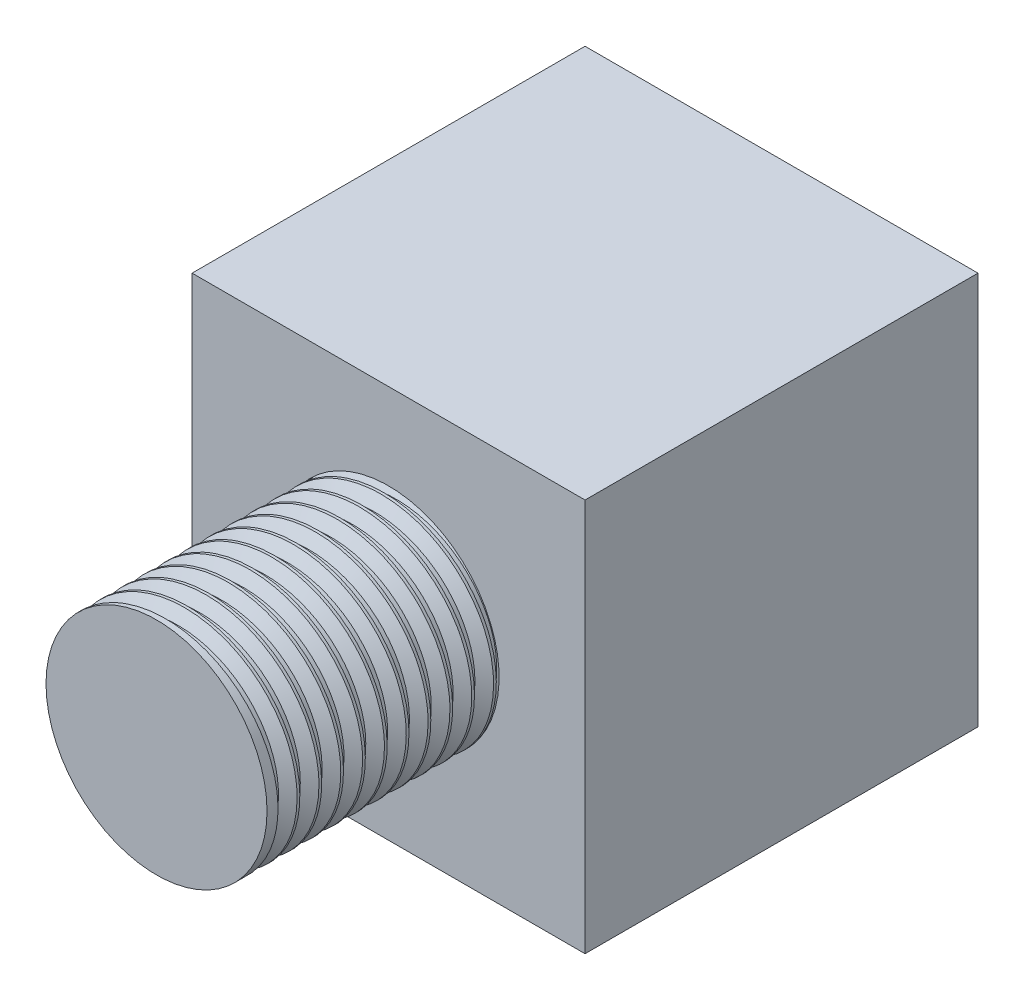
SolidWorks part; units mm, degrees
ref_plane "Front Plane" through (0, 0, 0) normal (0, 0, 1) x (1, 0, 0)
ref_plane "Top Plane" through (0, 0, 0) normal (0, 1, 0) x (1, 0, 0)
ref_plane "Right Plane" through (0, 0, 0) normal (1, 0, 0) x (0, 0, -1)
sketch "Sketch1" plane through (0, 0, 0) normal (0, 0, 1) x (1, 0, 0)
  line L1 (-12.7, -12.7) -> (12.7, -12.7)
  line L2 (-12.7, -12.7) -> (-12.7, 12.7)
  line L3 (-12.7, 12.7) -> (12.7, 12.7)
  line L4 (12.7, -12.7) -> (12.7, 12.7)
  line L5 (-12.7, -12.7) -> (12.7, 12.7) construction
  line L6 (-12.7, 12.7) -> (12.7, -12.7) construction
  point P0 (0, 0)
  dimension "D1" = 25.4
extrude "Boss-Extrude1" add sketch "Sketch1" along normal blind 25.4
sketch "Sketch2" plane through (0, 0, 25.4) normal (0, 0, 1) x (1, 0, 0)
  circle A0 centre (0, 0) radius 7.1438
  dimension "D1" = 14.2875
extrude "Boss-Extrude2" add sketch "Sketch2" along normal blind 15 contours A0
hole_wizard "9/16-18 Tapped Hole3" positions "Sketch4" profile "Sketch5" tap size "9/16-18" standard "ANSI Inch"
sketch "Sketch4" plane through (0, 0, 0) normal (0, 0, 1) x (1, 0, 0)
  point P0 (0, 0)
sketch "Sketch5" plane through (0, 0, 0) normal (1, 0, 0) x (0, 1, 0)
  line L0 (0, 0) -> (0, 18.9345)
  line L1 (0, 18.9345) -> (6.5481, 15)
  line L2 (6.5481, 15) -> (6.5481, 0)
  line L5 (6.5481, 0) -> (0, 0)
  line L10 (0, 18.9345) -> (-6.5481, 15) construction
  line L11 (0, -6.35) -> (0, 107.95) construction
  dimension "Tap Drill Dia." = 13.0962
  dimension "Tap Drill Depth" = 15
  dimension "Drill Angle" = 118
cosmetic thread "Hole Thread1" parameters "D1"=14, "D2"=14.2875
thread "Thread1" pitch 1.4111 method cut profile "Thread Profile1" start angle 0, offset 0, length 0, pitch 1.4111, diameter 14.2875
ref_plane "Plane1" through (-7.1438, 0, 40.4) normal (0, -1, 0) x (-1, 0, 0)
sketch "Thread Profile1" plane through (-7.1438, 0, 40.4) normal (0, -1, 0) x (-1, 0, 0)
  line L0 (0, 0) -> (0, 1.4111) construction
  line L11 (0, 0) -> (0, 1.2347)
  line L12 (0, 1.2347) -> (-0.7638, 0.7937)
  line L13 (-0.7638, 0.7937) -> (-0.7638, 0.441)
  line L15 (-0.7638, 0.441) -> (0, 0)
  line L17 (-0.7638, 0.6174) -> (0, 0.6174) construction
  point P2 (0, 0)
  dimension "Pitch" = 1.4111
  dimension "Profile_Angle" = 60
  dimension "Profile_Land" = 0.3528
  dimension "Profile_Height" = 0.7638
